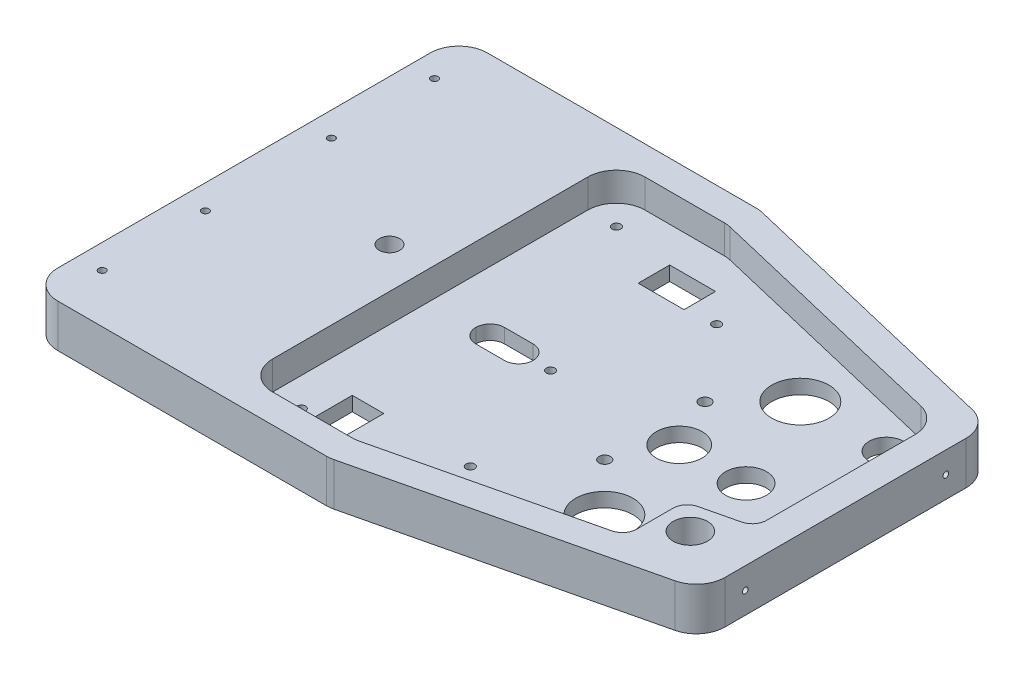
SolidWorks part; units mm, degrees
material "Carvalho"
ref_plane "Plano frontal" through (0, 0, 0) normal (0, 0, 1) x (1, 0, 0)
ref_plane "Plano superior" through (0, 0, 0) normal (0, 1, 0) x (1, 0, 0)
ref_plane "Plano direito" through (0, 0, 0) normal (1, 0, 0) x (0, 0, -1)
sketch "Esboço1" plane through (0, 0, 0) normal (0, 1, 0) x (1, 0, 0)
  line L0 (210, 50) -> (105, 75)
  line L1 (0, -75) -> (105, -75)
  line L2 (0, -75) -> (0, 75)
  line L3 (0, 75) -> (105, 75)
  line L4 (210, -50) -> (210, 50)
  line L7 (105, -75) -> (210, -50)
  line L8 (-14.8259, 0) -> (14.392, 0) construction
  line L9 (0, 21.2472) -> (0, -16.7598) construction
  circle A0 centre (50.8, 0) radius 3.5719
  circle A1 centre (175.26, 0) radius 7.14
  circle A2 centre (151.92, 0) radius 8
  circle A3 centre (151.92, 0) radius 8 construction
  circle A4 centre (8.5, -58) radius 1.25
  circle A5 centre (8.5, -22) radius 1.25
  circle A6 centre (8.5, -58) radius 2.5 construction
  circle A7 centre (8.5, -22) radius 2.5 construction
  circle A8 centre (8.5, 22) radius 1.25
  circle A9 centre (8.5, 58) radius 1.25
  point P0 (0, 0)
  dimension "D3" = 7.1437
  dimension "D5" = 14.28
  dimension "D9" = 2.5
  dimension "D1" = 25
  dimension "D2" = 150
  dimension "D4" = 50.8
  dimension "D6" = 210
  dimension "D7" = 175.26
  dimension "D8" = 105
extrude "Ressalto-extrusão1" add sketch "Esboço1" along normal blind 15
sketch "Esboço2" plane through (210, 0, 0) normal (1, 0, 0) x (0, 0, -1)
  line L0 (0, 15) -> (0, 0) construction
  line L1 (-50, 15) -> (50, 15) construction
  circle A0 centre (35, 7.5) radius 1
  circle A1 centre (-35, 7.5) radius 1
  point P9 (0, 7.5)
  dimension "D1" = 2
  dimension "D2" = 35
extrude "Corte-extrusão1" cut sketch "Esboço2" against normal blind 10
sketch "Esboço3" plane through (0, 15, 0) normal (0, 1, 0) x (1, 0, 0)
  line L0 (200, 42.1014) -> (200, -42.1014)
  line L2 (65, -65) -> (65, 65)
  line L6 (210, -50) -> (210, 50) construction
  line L7 (0, 75) -> (0, -75) construction
  line L8 (-22.821, 0) -> (224.4652, 0) construction
  line L9 (65, 65) -> (103.8259, 65)
  line L10 (103.8259, 65) -> (200, 42.1014)
  line L11 (65, -65) -> (103.8259, -65)
  line L12 (103.8259, -65) -> (200, -42.1014)
  line L13 (105, -75) -> (210, -50) construction
  line L14 (0, -75) -> (105, -75) construction
  line L15 (180, -26.3042) -> (200, -21.5423)
  line L16 (180, -46.8633) -> (180, -26.3042)
  circle M12 centre (151.92, 0) radius 8
  circle M14 centre (175.26, 0) radius 7.14
  dimension "D1" = 10
  dimension "D2" = 65
  dimension "D3" = 10
  dimension "D4" = 10
  dimension "D5" = 20
  dimension "D6" = 20
extrude "Corte-extrusão2" cut sketch "Esboço3" against normal blind 10 contours L2 L8 L0 L10 L9 M12 M14 | L8 L2 L11 L12 L16 L15 L0 M14 M12 region at (122.8919, 15, 29.2811) region at (126.5743, 15, -29.5512)
fillet "Filete1" radius 10 11 edges at (105, 7.5, 75) (0, 7.5, 75) (0, 7.5, -75) (210, 7.5, 50) (105, 7.5, -75) (210, 7.5, -50) (200, 10, -42.1014) (103.8259, 10, 65) (65, 10, 65) (103.8259, 10, -65) (65, 10, -65)
sketch "Esboço5" plane through (0, 0, 0) normal (0, -1, 0) x (1, 0, 0)
  line L0 (175.26, 0) -> (90.92, 0) construction
  line L2 (143.42, 17.5) -> (143.42, -17.5) construction
  line L3 (175.26, 0) -> (101.1849, 0) construction
  line L8 (80.92, -5) -> (100.92, -5)
  line L9 (80.92, -5) -> (80.92, 5)
  line L10 (80.92, 5) -> (100.92, 5)
  line L11 (100.92, -5) -> (100.92, 5)
  line L12 (80.92, -5) -> (100.92, 5) construction
  line L13 (80.92, 5) -> (100.92, -5) construction
  circle A0 centre (143.42, 17.5) radius 2
  circle A1 centre (143.42, -17.5) radius 2
  point P5 (143.42, 0)
  dimension "D6" = 4
  dimension "D1" = 35
  dimension "D2" = 42.5
  dimension "D3" = 20
  dimension "D4" = 31.84
  dimension "D5" = 10
extrude "Corte-extrusão4" cut sketch "Esboço5" against normal through all
fillet "Filete2" radius 5 4 edges at (80.92, 2.5, -5) (80.92, 2.5, 5) (100.92, 2.5, 5) (100.92, 2.5, -5)
fillet "Filete3" radius 5 3 edges at (180, 10, 46.8633) (180, 10, 26.3042) (200, 10, 21.5423)
sketch "Esboço6" plane through (0, 15, 0) normal (0, 1, 0) x (1, 0, 0)
  line L0 (224.3981, 0) -> (150.0179, 0) construction
  circle A0 centre (190, -34.2028) radius 6
  circle A1 centre (190, 34.2028) radius 6
  circle A2 centre (160, 34.2028) radius 10
  arc A3 (200, 34.2028) -> (192.3162, 43.9309) centre (190, 34.2028) ccw construction
  circle A4 centre (160, -34.2028) radius 10
  dimension "D1" = 12
  dimension "D2" = 20
  dimension "D3" = 30
extrude "Corte-extrusão5" cut sketch "Esboço6" against normal through all
sketch "Esboço7" plane through (0, 0, 0) normal (0, -1, 0) x (1, 0, 0)
  line L0 (-8.8077, 0) -> (220.236, 0) construction
  line L1 (65, 55) -> (65, -55) construction
  line L3 (90.9, 58.1) -> (79.9, 58.1)
  line L4 (90.9, 58.1) -> (90.9, 42.1)
  line L5 (90.9, 42.1) -> (79.9, 42.1)
  line L6 (79.9, 58.1) -> (79.9, 42.1)
  line L7 (111.9, -41.7) -> (95.9, -41.7)
  line L8 (111.9, -41.7) -> (111.9, -52.7)
  line L9 (111.9, -52.7) -> (95.9, -52.7)
  line L10 (95.9, -41.7) -> (95.9, -52.7)
  line L11 (80.4, 57.6) -> (90.4, 57.6) construction
  line L12 (80.4, 57.6) -> (80.4, 42.6) construction
  line L13 (85.4, 58.1) -> (85.4, 42.1) construction
  line L14 (96.4, -52.2) -> (96.4, -42.2) construction
  line L15 (96.4, -52.2) -> (111.4, -52.2) construction
  circle A3 centre (75, 55) radius 1.5
  circle A5 centre (122, 43) radius 1.5
  circle A6 centre (107, 0) radius 1.5
  circle A7 centre (75, -55) radius 1.5
  circle A8 centre (122, -43) radius 1.5
  dimension "D1" = 55
  dimension "D2" = 3
  dimension "D3" = 43
  dimension "D4" = 47
  dimension "D5" = 10
  dimension "D6" = 32
  dimension "D7" = 11
  dimension "D8" = 0.5
  dimension "D9" = 0.5
  dimension "D10" = 16
  dimension "D11" = 16
  dimension "D12" = 11
  dimension "D13" = 0.5
  dimension "D14" = 0.5
extrude "Corte-extrusão6" cut sketch "Esboço7" against normal through all contours A3 | A6 | A5 | A7 | A8 | L6 L5 L4 L3 | L7 L10 L9 L8
